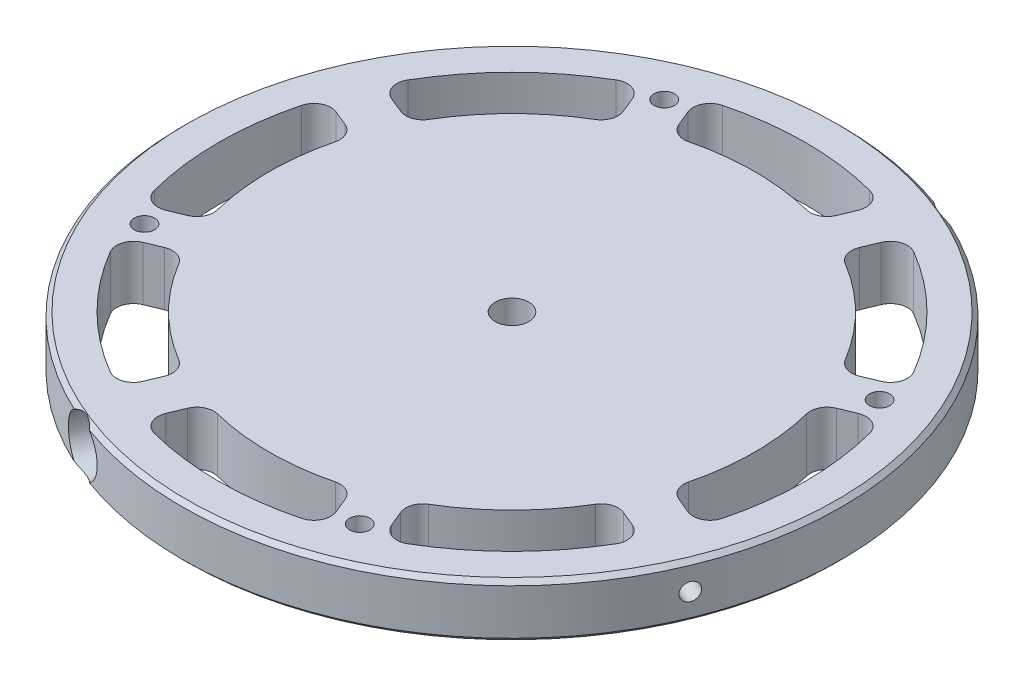
SolidWorks part; units mm, degrees
material "6061-T6 (SS)"
ref_plane "Front Plane" through (0, 0, 0) normal (0, 0, 1) x (1, 0, 0)
ref_plane "Top Plane" through (0, 0, 0) normal (0, 1, 0) x (1, 0, 0)
ref_plane "Right Plane" through (0, 0, 0) normal (1, 0, 0) x (0, 0, -1)
sketch "Sketch2" plane through (0, 0, 0) normal (1, 0, 0) x (0, 0, -1)
  line L0 (0, 0) -> (-77.55, 0)
  line L1 (-77.55, 0) -> (-77.55, 12.7)
  line L2 (-77.55, 12.7) -> (0, 12.7)
  line L5 (0, 12.7) -> (0, 0)
  dimension "D1" = 77.55
  dimension "D2" = 12.7
ref_axis "Axis1" through (0, -0.8888, 0) along (0, 1, 0)
revolve "Revolve1" add sketch "Sketch2" angle 360 about axis through (0, -0.8888, 0) along (0, 1, 0)
hole_wizard "#12 (0.189) Diameter Hole1" positions "Sketch6" profile "Sketch7" hole size "#12" standard "ANSI Inch" end condition through all
sketch "Sketch6" plane through (0, 12.7, 0) normal (0, 1, 0) x (1, 0, 0)
  line L0 (0, 0) -> (-53.438, 129.0108) construction
  line L2 (0, 0) -> (0, 109.0908) construction
  point P0 (-25.3336, 61.1608)
  dimension "D1" = 22.5
  dimension "D2" = 66.2
sketch "Sketch7" plane through (-25.3336, 12.7, -61.1608) normal (1, 0, 0) x (0, 0, 1)
  line L0 (0, 0) -> (0, 12.7)
  line L1 (0, 12.7) -> (2.4003, 12.7)
  line L2 (2.4003, 12.7) -> (2.4003, 0)
  line L5 (2.4003, 0) -> (0, 0)
  line L11 (0, -6.35) -> (0, 107.95) construction
  dimension "Thru Hole Dia." = 4.8006
  dimension "Thru Hole Depth" = 12.7
pattern_circular "CirPattern3" count 4 over 360 about axis through (0, -0.8888, 0) along (0, 1, 0) of "#12 (0.189) Diameter Hole1"
sketch "Sketch8" plane through (0, 12.7, 0) normal (0, 1, 0) x (1, 0, 0)
  line L4 (0, 0) -> (0, 93.9995) construction
  line L5 (0, 0) -> (113.8372, 0) construction
  line L6 (-17.1671, 54.5107) -> (-21.7355, 65.5398)
  line L7 (17.1671, 54.5107) -> (21.7355, 65.5398)
  line L8 (0, 0) -> (-25.3336, 61.1608) construction
  arc A0 (-17.1671, 54.5107) -> (17.1671, 54.5107) centre (0, 0) cw
  arc A1 (-21.7355, 65.5398) -> (21.7355, 65.5398) centre (0, 0) cw
  circle A2 centre (0, 0) radius 77.55 construction
  dimension "D1" = 57.15
  dimension "D2" = 8.5
  dimension "D3" = 5
extrude "Cut-Extrude1" cut sketch "Sketch8" against normal through all
fillet "Fillet1" radius 4 4 edges at (17.1671, 6.35, -54.5107) (21.7355, 6.35, -65.5398) (-17.1671, 6.35, -54.5107) (-21.7355, 6.35, -65.5398)
pattern_circular "CirPattern4" count 8 over 360 about axis through (0, -0.8888, 0) along (0, 1, 0) of "Cut-Extrude1", "Fillet1"
chamfer "Chamfer1" distance 1 angle 45 2 edges at (0, 0, -77.55) (0, 12.7, -77.55)
ref_plane "Plane1" through (0, 0, 0) normal (0.9239, 0, 0.3827) x (0, 1, 0)
hole_wizard "#20 (0.161) Diameter Hole1" positions "Sketch16" profile "Sketch15" hole size "#20" standard "ANSI Inch" end condition through all
sketch "Sketch16" plane through (0, 0, 0) normal (0.9239, 0, 0.3827) x (0, 1, 0)
  point P0 (6.35, 0)
  dimension "D1" = 6.35
sketch "Sketch15" plane through (0, 6.35, 0) normal (0, 1, 0) x (-0.3827, 0, 0.9239)
  line L0 (0, 0) -> (0, 101.324)
  line L1 (0, 101.324) -> (2.0447, 101.324)
  line L2 (2.0447, 101.324) -> (2.0447, 0)
  line L5 (2.0447, 0) -> (0, 0)
  line L11 (0, -6.35) -> (0, 107.95) construction
  dimension "Thru Hole Dia." = 4.0894
  dimension "Thru Hole Depth" = 101.324
ref_plane "Plane2" through (29.6771, 0, -71.6469) normal (0.3827, 0, -0.9239) x (-0.9239, 0, -0.3827)
sketch "Sketch19" plane through (29.6771, 0, -71.6469) normal (0.3827, 0, -0.9239) x (-0.9239, 0, -0.3827)
  line L0 (-76.55, 0) -> (76.55, 0) construction
  line L2 (0, -0.8888) -> (0, 13.5888) construction
  circle A0 centre (0, 6.35) radius 5.5625 construction
  circle A1 centre (0, 6.35) radius 6.25
  dimension "D1" = 12.5
  dimension "D2" = 6.35
extrude "Cut-Extrude3" cut sketch "Sketch19" against normal blind 5
pattern_circular "CirPattern5" count 2 over 360 about axis through (0, -0.8888, 0) along (0, 1, 0) of "Cut-Extrude3"
hole_wizard "#10-24 Tapped Hole1" positions "Sketch20" profile "Sketch21" tap size "#10-24" standard "ANSI Inch"
sketch "Sketch20" plane through (-27.7637, 0, 67.0275) normal (-0.3827, 0, 0.9239) x (0.9239, 0, 0.3827)
  circle A0 centre (0, 6.35) radius 6.25
  circle A1 centre (0, 6.35) radius 6.25 construction
  point P0 (0, 6.35)
sketch "Sketch21" plane through (-27.7637, 6.35, 67.0275) normal (0, 1, 0) x (0.9239, 0, 0.3827)
  line L0 (0, 0) -> (0, 51.9408)
  line L1 (0, 51.9408) -> (1.8986, 50.8)
  line L2 (1.8986, 50.8) -> (1.8986, 0)
  line L5 (1.8986, 0) -> (0, 0)
  line L10 (0, 51.9408) -> (-1.8986, 50.8) construction
  line L11 (0, -6.35) -> (0, 107.95) construction
  dimension "Tap Drill Dia." = 3.7973
  dimension "Tap Drill Depth" = 50.8
  dimension "Drill Angle" = 118
pattern_circular "CirPattern6" count 2 over 360 about axis through (0, -0.8888, 0) along (0, 1, 0) of "#10-24 Tapped Hole1"
sketch "Sketch22" plane through (0, 12.7, 0) normal (0, 1, 0) x (1, 0, 0)
  circle A0 centre (0, 0) radius 3.9688
  dimension "D1" = 7.9375
extrude "Cut-Extrude4" cut sketch "Sketch22" against normal blind 12.8
equation "\"TubeDiameter\" = 6.500in"
equation "\"D1@Sketch2\"=(\"TubeDiameter\"/2)-5mm"
equation "\"D2@Sketch6\"=66.2"
